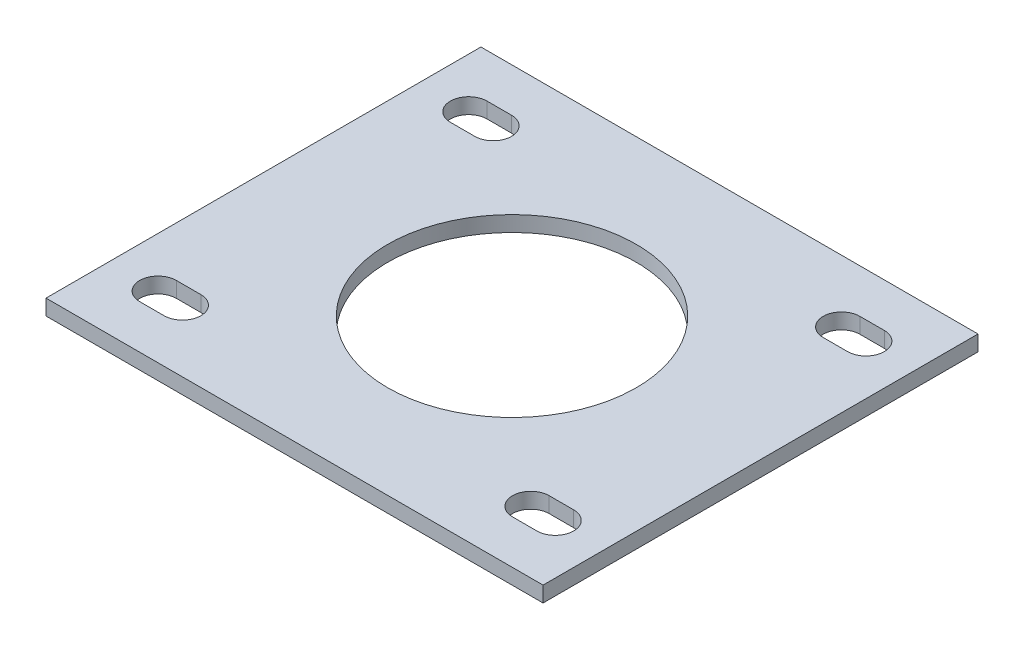
SolidWorks part; units mm, degrees
material "1023 Carbon Steel Sheet (SS)"
ref_plane "Front Plane" through (0, 0, 0) normal (0, 0, 1) x (1, 0, 0)
ref_plane "Top Plane" through (0, 0, 0) normal (0, 1, 0) x (1, 0, 0)
ref_plane "Right Plane" through (0, 0, 0) normal (1, 0, 0) x (0, 0, -1)
sketch "Sketch1" plane through (0, 0, 0) normal (0, 1, 0) x (1, 0, 0)
  line L1 (50.8, -44.45) -> (-50.8, -44.45)
  line L2 (50.8, -44.45) -> (50.8, 44.45)
  line L3 (50.8, 44.45) -> (-50.8, 44.45)
  line L4 (-50.8, -44.45) -> (-50.8, 44.45)
  line L5 (50.8, -44.45) -> (-50.8, 44.45) construction
  line L6 (50.8, 44.45) -> (-50.8, -44.45) construction
  circle A0 centre (0, 0) radius 25.4
  point P0 (0, 0)
  dimension "D3" = 50.8
  dimension "D1" = 88.9
  dimension "D2" = 101.6
extrude "Boss-Extrude1" add sketch "Sketch1" along normal blind 3.175
sketch "Sketch2" plane through (0, 3.175, 0) normal (0, 1, 0) x (1, 0, 0)
  line L0 (-40.6, 31.75) -> (-35.6, 31.75) construction
  line L1 (-40.6, 35.5) -> (-35.6, 35.5)
  line L2 (-40.6, 28) -> (-35.6, 28)
  line L3 (-38.1, 31.75) -> (-38.1, -31.75) construction
  line L4 (-40.6, -31.75) -> (-35.6, -31.75) construction
  line L5 (-40.6, -28) -> (-35.6, -28)
  line L6 (-40.6, -35.5) -> (-35.6, -35.5)
  line L7 (35.6, 31.75) -> (40.6, 31.75) construction
  line L8 (35.6, 35.5) -> (40.6, 35.5)
  line L9 (35.6, 28) -> (40.6, 28)
  line L10 (38.1, 31.75) -> (38.1, -31.75) construction
  line L11 (35.6, -31.75) -> (40.6, -31.75) construction
  line L12 (35.6, -28) -> (40.6, -28)
  line L13 (35.6, -35.5) -> (40.6, -35.5)
  line L14 (-38.1, -31.75) -> (38.1, -31.75) construction
  line L15 (-50.8, 44.45) -> (-50.8, -44.45) construction
  arc A0 (-40.6, 35.5) -> (-40.6, 28) centre (-40.6, 31.75) ccw
  arc A1 (-35.6, 28) -> (-35.6, 35.5) centre (-35.6, 31.75) ccw
  arc A2 (-40.6, -28) -> (-40.6, -35.5) centre (-40.6, -31.75) ccw
  arc A3 (-35.6, -35.5) -> (-35.6, -28) centre (-35.6, -31.75) ccw
  arc A4 (35.6, 35.5) -> (35.6, 28) centre (35.6, 31.75) ccw
  arc A5 (40.6, 28) -> (40.6, 35.5) centre (40.6, 31.75) ccw
  arc A6 (35.6, -28) -> (35.6, -35.5) centre (35.6, -31.75) ccw
  arc A7 (40.6, -35.5) -> (40.6, -28) centre (40.6, -31.75) ccw
  point P2 (-38.1, 31.75)
  point P11 (-38.1, -31.75)
  point P16 (0, -31.75)
  point P17 (-38.1, 0)
  point P21 (38.1, 31.75)
  point P30 (38.1, -31.75)
  point P35 (38.1, 0)
  point P38 (0, 0)
  dimension "D1" = 7.5
  dimension "D2" = 5
  dimension "D3" = 63.5
  dimension "D4" = 12.7
extrude "Cut-Extrude1" cut sketch "Sketch2" against normal through all
sketch "Sketch3" [suppressed] plane through (0, 3.175, 0) normal (0, 1, 0) x (1, 0, 0)
  line L0 (40.6, 35.5) -> (35.6, 35.5) construction
  line L1 (35.6, 28) -> (40.6, 28) construction
  line L2 (40.6, -28) -> (35.6, -28) construction
  line L3 (35.6, -35.5) -> (40.6, -35.5) construction
  line L4 (-50.8, 44.45) -> (-50.8, -44.45)
  line L5 (-50.8, -44.45) -> (50.8, -44.45)
  line L6 (50.8, -44.45) -> (50.8, 44.45)
  line L7 (50.8, 44.45) -> (-50.8, 44.45)
  line L8 (-50.8, 44.45) -> (-50.8, -44.45)
  line L9 (-50.8, -44.45) -> (50.8, -44.45)
  line L10 (50.8, -44.45) -> (50.8, 44.45)
  line L11 (50.8, 44.45) -> (-50.8, 44.45)
  line L12 (-35.6, -28) -> (-40.6, -28) construction
  line L13 (-40.6, -35.5) -> (-35.6, -35.5) construction
  line L14 (-35.6, 35.5) -> (-40.6, 35.5) construction
  line L15 (-40.6, 28) -> (-35.6, 28) construction
  line L16 (40.6, 35.5) -> (35.6, 35.5)
  line L17 (35.6, 28) -> (40.6, 28)
  line L18 (40.6, -28) -> (35.6, -28)
  line L19 (35.6, -35.5) -> (40.6, -35.5)
  line L20 (-35.6, -28) -> (-40.6, -28)
  line L21 (-40.6, -35.5) -> (-35.6, -35.5)
  line L22 (-35.6, 35.5) -> (-40.6, 35.5)
  line L23 (-40.6, 28) -> (-35.6, 28)
  arc A0 (40.6, 28) -> (40.6, 35.5) centre (40.6, 31.75) ccw construction
  arc A1 (35.6, 35.5) -> (35.6, 28) centre (35.6, 31.75) ccw construction
  arc A2 (40.6, -35.5) -> (40.6, -28) centre (40.6, -31.75) ccw construction
  arc A3 (35.6, -28) -> (35.6, -35.5) centre (35.6, -31.75) ccw construction
  arc A4 (-35.6, -35.5) -> (-35.6, -28) centre (-35.6, -31.75) ccw construction
  arc A5 (-40.6, -28) -> (-40.6, -35.5) centre (-40.6, -31.75) ccw construction
  arc A6 (-40.6, 35.5) -> (-40.6, 28) centre (-40.6, 31.75) ccw construction
  arc A7 (-35.6, 28) -> (-35.6, 35.5) centre (-35.6, 31.75) ccw construction
  circle A8 centre (0, 0) radius 25.4 construction
  arc A9 (40.6, 28) -> (40.6, 35.5) centre (40.6, 31.75) ccw
  arc A10 (35.6, 35.5) -> (35.6, 28) centre (35.6, 31.75) ccw
  arc A11 (40.6, -35.5) -> (40.6, -28) centre (40.6, -31.75) ccw
  arc A12 (35.6, -28) -> (35.6, -35.5) centre (35.6, -31.75) ccw
  arc A13 (-35.6, -35.5) -> (-35.6, -28) centre (-35.6, -31.75) ccw
  arc A14 (-40.6, -28) -> (-40.6, -35.5) centre (-40.6, -31.75) ccw
  arc A15 (-40.6, 35.5) -> (-40.6, 28) centre (-40.6, 31.75) ccw
  arc A16 (-35.6, 28) -> (-35.6, 35.5) centre (-35.6, 31.75) ccw
  circle A17 centre (0, 0) radius 25.4
  dimension "D1" = 0
extrude "Boss-Extrude2" [suppressed] add sketch "Sketch3" along normal blind 3.175
sketch "Sketch5" [suppressed] plane through (0, 0, 0) normal (0, -1, 0) x (1, 0, 0)
  circle A0 centre (0, 0) radius 22.225
  circle A1 centre (0, 0) radius 31.75
  dimension "D1" = 44.45
  dimension "D2" = 63.5
extrude "Boss-Extrude3" [suppressed] add sketch "Sketch5" against normal blind 3.175
